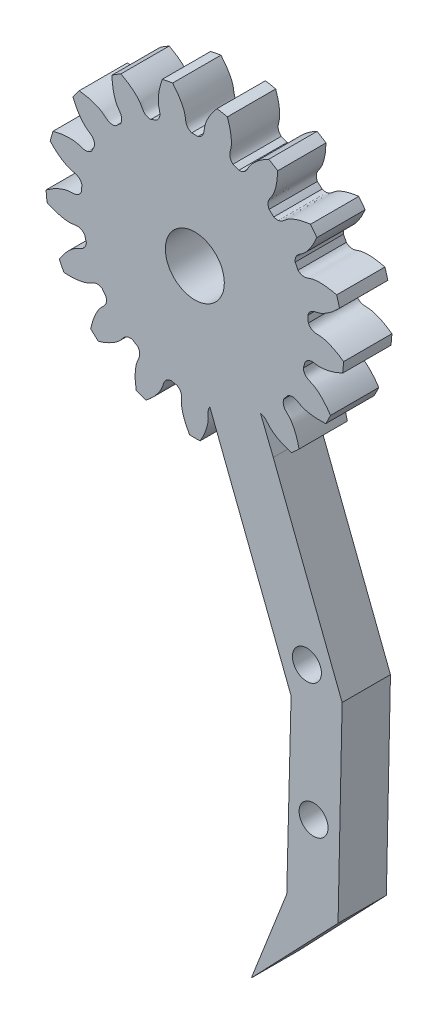
SolidWorks part; units mm, degrees
material "45"
ref_plane "前视基准面" through (0, 0, 0) normal (0, 0, 1) x (1, 0, 0)
ref_plane "上视基准面" through (0, 0, 0) normal (0, 1, 0) x (1, 0, 0)
ref_plane "右视基准面" through (0, 0, 0) normal (1, 0, 0) x (0, 0, -1)
sketch "草图1" plane through (0, 0, 0) normal (0, 0, 1) x (1, 0, 0)
  circle A0 centre (0, 0) radius 15.4185
extrude "凸台-拉伸1" add sketch "草图1" along normal blind 5
ref_axis "基准轴1" through (0, 0, 5) along (0, 0, -1)
sketch "草图2" plane through (0, 0, 0) normal (0, 0, 1) x (1, 0, 0)
  line L0 (0, 0) -> (0, 15.4185) construction
  circle A0 centre (0, 0) radius 15.4185 construction
  arc A1 (0.3273, 11.7622) -> (-0.3273, 11.7622) centre (0, 0) ccw
  arc A2 (5.0567, 17.4322) -> (-5.0567, 17.4322) centre (0, 0) ccw
  spline S0 degree 3 poles (0.3273, 11.7622) (1.019, 12.0505) (0.9189, 12.5861) (1.036, 13.0892) (1.0468, 13.1319) (1.0598, 13.1794) (1.0753, 13.2316) (1.0934, 13.2885) (1.1143, 13.3498) (1.1382, 13.4156) (1.1652, 13.4858) (1.1956, 13.5602) (1.2296, 13.6388) (1.2672, 13.7213) (1.3088, 13.8078) (1.3544, 13.898) (1.4042, 13.9919) (1.4584, 14.0894) (1.5172, 14.1902) (1.5807, 14.2942) (1.649, 14.4013) (1.7223, 14.5113) (1.8008, 14.6242) (1.8846, 14.7396) (1.9737, 14.8574) (2.0685, 14.9775) (2.1689, 15.0997) (2.2751, 15.2239) (2.3872, 15.3497) (2.5053, 15.4771) (2.6296, 15.6058) (2.7601, 15.7356) (2.8969, 15.8665) (3.0401, 15.998) (3.1898, 16.1301) (3.346, 16.2625) (3.5089, 16.3951) (3.6785, 16.5276) (3.8549, 16.6597) (4.0381, 16.7913) (4.2282, 16.9222) (4.4251, 17.0521) (4.6999, 17.2256) (4.9121, 17.3507) (5.0567, 17.4322) knots 0 0 0 0 0.193883 0.199024 0.204851 0.211363 0.21856 0.226443 0.235011 0.244265 0.254205 0.264829 0.27614 0.288136 0.300817 0.314184 0.328236 0.342973 0.358397 0.374505 0.391299 0.408779 0.426944 0.445795 0.465331 0.485552 0.506459 0.528051 0.550329 0.573293 0.596941 0.621276 0.646296 0.672001 0.698392 0.725468 0.753229 0.781677 0.810809 0.840627 0.871131 0.90232 0.934195 1 1 1 1
  spline S1 degree 3 poles (-0.3273, 11.7622) (-1.019, 12.0505) (-0.9189, 12.5861) (-1.036, 13.0892) (-1.0468, 13.1319) (-1.0598, 13.1794) (-1.0753, 13.2316) (-1.0934, 13.2885) (-1.1143, 13.3498) (-1.1382, 13.4156) (-1.1652, 13.4858) (-1.1956, 13.5602) (-1.2296, 13.6388) (-1.2672, 13.7213) (-1.3088, 13.8078) (-1.3544, 13.898) (-1.4042, 13.9919) (-1.4584, 14.0894) (-1.5172, 14.1902) (-1.5807, 14.2942) (-1.649, 14.4013) (-1.7223, 14.5113) (-1.8008, 14.6242) (-1.8846, 14.7396) (-1.9737, 14.8574) (-2.0685, 14.9775) (-2.1689, 15.0997) (-2.2751, 15.2239) (-2.3872, 15.3497) (-2.5053, 15.4771) (-2.6296, 15.6058) (-2.7601, 15.7356) (-2.8969, 15.8665) (-3.0401, 15.998) (-3.1898, 16.1301) (-3.346, 16.2625) (-3.5089, 16.3951) (-3.6785, 16.5276) (-3.8549, 16.6597) (-4.0381, 16.7913) (-4.2282, 16.9222) (-4.4251, 17.0521) (-4.6999, 17.2256) (-4.9121, 17.3507) (-5.0567, 17.4322) knots 0 0 0 0 0.193883 0.199024 0.204851 0.211363 0.21856 0.226443 0.235011 0.244265 0.254205 0.264829 0.27614 0.288136 0.300817 0.314184 0.328236 0.342973 0.358397 0.374505 0.391299 0.408779 0.426944 0.445795 0.465331 0.485552 0.506459 0.528051 0.550329 0.573293 0.596941 0.621276 0.646296 0.672001 0.698392 0.725468 0.753229 0.781677 0.810809 0.840627 0.871131 0.90232 0.934195 1 1 1 1
extrude "切除-拉伸1" cut sketch "草图2" along normal through all
pattern_circular "阵列(圆周)1" count 17 over 360 about axis through (0, 0, 5) along (0, 0, -1) of "切除-拉伸1"
sketch "草图3" plane through (0, 0, 0) normal (0, 0, 1) x (1, 0, 0)
  circle A0 centre (0, 0) radius 13.7955 construction
  dimension "Dn" = 27.591
sketch "草图4" plane through (0, 0, 5) normal (0, 0, 1) x (1, 0, 0)
  circle A0 centre (0, 0) radius 3.05
  dimension "D1" = 6.1
extrude "切除-拉伸2" cut sketch "草图4" against normal blind 10
sketch "草图11" plane through (0, 0, 0) normal (0, 0, -1) x (-1, 0, 0)
  line L3 (0, 0) -> (-5.5698, -14.3773) construction
  line L4 (-8.1168, -13.1091) -> (-5.6495, -6.9382)
  line L18 (-5.6495, -6.9382) -> (-0.4992, -8.9334)
  line L19 (-8.1168, -13.1091) -> (-15.2438, -31.506)
  line L20 (-14.8209, -51.5015) -> (-15.2438, -31.506)
  line L21 (-5.8389, -60.8996) -> (-14.8209, -51.5015)
  line L22 (-9.5102, -51.5473) -> (-5.8389, -60.8996)
  line L23 (-9.9601, -33.5529) -> (-9.5102, -51.5473)
  line L24 (-2.8331, -15.156) -> (-9.8789, -33.3432)
  line L25 (-2.8331, -15.156) -> (-0.4325, -8.9593)
  line L26 (-9.9601, -33.5529) -> (-9.8789, -33.3432)
  line L28 (-0.4992, -8.9334) -> (-0.4325, -8.9593)
  arc A0 (-6.0744, -14.1715) -> (-5.0582, -14.5652) centre (0, 0) ccw construction
  point P1 (0, 0)
extrude "凸台-拉伸2" add sketch "草图11" against normal blind 5
sketch "草图15" plane through (0, 0, 0) normal (0, 0, -1) x (-1, 0, 0)
  circle A0 centre (-11.5974, -29.945) radius 1.5
  circle A1 centre (-12.2878, -43.4782) radius 1.5
extrude "切除-拉伸3" cut sketch "草图15" against normal blind 10
